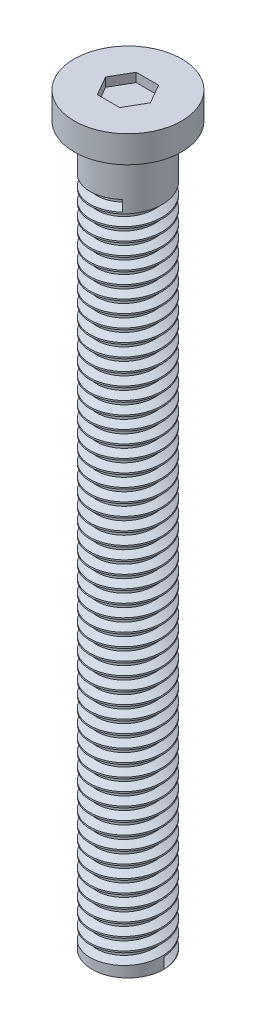
SolidWorks part; units mm, degrees
ref_plane "Front" through (0, 0, 0) normal (0, 0, 1) x (1, 0, 0)
ref_plane "Top" through (0, 0, 0) normal (0, 1, 0) x (1, 0, 0)
ref_plane "Right" through (0, 0, 0) normal (1, 0, 0) x (0, 0, -1)
sketch "Sketch1" plane through (0, 0, 0) normal (0, 1, 0) x (1, 0, 0)
  circle A0 centre (0, 0) radius 2
  dimension "D1" = 4
extrude "Boss-Extrude1" add sketch "Sketch1" along normal blind 40
sketch "Sketch2" plane through (0, 40, 0) normal (0, 1, 0) x (1, 0, 0)
  circle A1 centre (0, 0) radius 3
  dimension "D1" = 6
extrude "Boss-Extrude2" add sketch "Sketch2" along normal blind 1.5
sketch "Sketch3" plane through (0, 41.5, 0) normal (0, 1, 0) x (1, 0, 0)
  line L1 (0.625, -1.0825) -> (1.25, 0)
  line L2 (1.25, 0) -> (0.625, 1.0825)
  line L3 (0.625, 1.0825) -> (-0.625, 1.0825)
  line L4 (-0.625, 1.0825) -> (-1.25, 0)
  line L5 (-1.25, 0) -> (-0.625, -1.0825)
  line L6 (-0.625, -1.0825) -> (0.625, -1.0825)
  circle A0 centre (0, 0) radius 1.0825 construction
  dimension "D1" = 1.25
extrude "Cut-Extrude1" cut sketch "Sketch3" against normal blind 0.5
thread "Thread1" pitch 0.7 method cut profile "Thread Profile1" start angle 0, offset 0, length 37, pitch 0.7, diameter 4
ref_plane "Plane1" through (2, 0, 0) normal (0, 0, 1) x (1, 0, 0)
sketch "Thread Profile1" plane through (2, 0, 0) normal (0, 0, 1) x (1, 0, 0)
  line L0 (0, 0) -> (0, 0.7) construction
  line L11 (0, 0) -> (0, 0.6125)
  line L12 (0, 0.6125) -> (-0.3789, 0.3937)
  line L13 (-0.3789, 0.3937) -> (-0.3789, 0.2187)
  line L15 (-0.3789, 0.2187) -> (0, 0)
  line L17 (-0.3789, 0.3062) -> (0, 0.3062) construction
  point P2 (0, 0)
  dimension "Pitch" = 0.7
  dimension "Profile_Angle" = 60
  dimension "Profile_Land" = 0.175
  dimension "Profile_Height" = 0.3789
